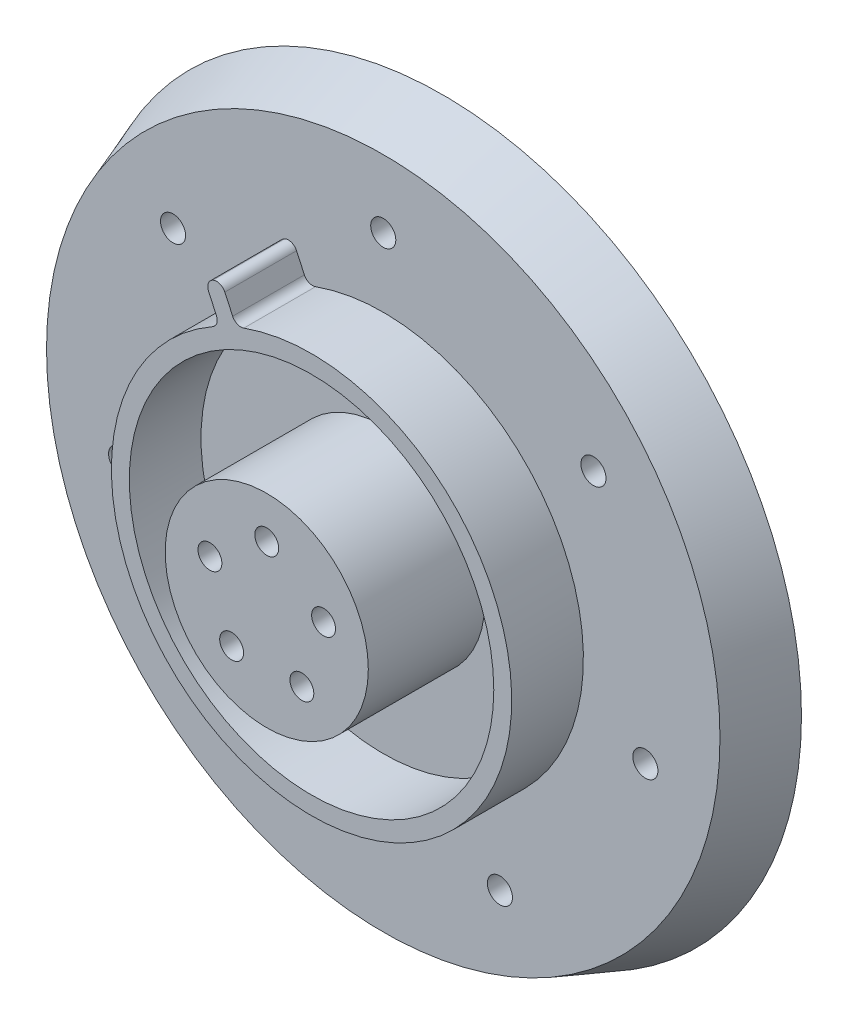
SolidWorks part; units mm, degrees
ref_plane "Plano frontal" through (0, 0, 0) normal (0, 0, 1) x (1, 0, 0)
ref_plane "Plano superior" through (0, 0, 0) normal (0, 1, 0) x (1, 0, 0)
ref_plane "Plano direito" through (0, 0, 0) normal (1, 0, 0) x (0, 0, -1)
sketch "Esboço1" plane through (0, 0, 0) normal (0, 0, 1) x (1, 0, 0)
  circle A0 centre (0, 0) radius 60
  dimension "D1" = 120
extrude "Ressalto-extrusão1" add sketch "Esboço1" along normal blind 10
sketch "Esboço2" plane through (0, 0, 10) normal (0, 0, 1) x (1, 0, 0)
  circle A0 centre (0, 0) radius 17
  dimension "D1" = 34
extrude "Ressalto-extrusão2" add sketch "Esboço2" along normal blind 19.5
sketch "Esboço3" plane through (0, 0, 10) normal (0, 0, 1) x (1, 0, 0)
  line L0 (-13.9923, 30.4379) -> (-16.4984, 35.8895) construction
  line L1 (-17.8613, 35.263) -> (-15.1355, 36.516)
  line L2 (-17.8613, 35.263) -> (-15.3411, 29.7809)
  line L3 (-15.1355, 36.516) -> (-12.6154, 31.0339)
  circle A0 centre (0, 0) radius 30.5
  arc A1 (-15.3411, 29.7809) -> (-12.6154, 31.0339) centre (0, 0) ccw
  point P9 (-16.4984, 35.8895)
  point P12 (-16.4984, 35.8895)
  dimension "D1" = 61
  dimension "D2" = 67
  dimension "D3" = 6
  dimension "D4" = 3
extrude "Ressalto-extrusão3" add sketch "Esboço3" along normal blind 12
sketch "Esboço4" plane through (0, 0, 10) normal (0, 0, 1) x (1, 0, 0)
  circle A0 centre (0, 45) radius 2.1
  circle A6 centre (35.1824, 28.057) radius 2.1
  circle A7 centre (43.8718, -10.0134) radius 2.1
  circle A8 centre (19.5248, -40.5436) radius 2.1
  circle A9 centre (-19.5248, -40.5436) radius 2.1
  circle A10 centre (-43.8718, -10.0134) radius 2.1
  circle A11 centre (-35.1824, 28.057) radius 2.1
  point P16 (0, 0)
  point P18 (0, 0)
  dimension "D1" = 4.2
  dimension "D2" = 45
  dimension "D3" = 7
extrude "Corte-extrusão1" cut sketch "Esboço4" against normal up to surface (10 mm away) up to face at (60, 0, 0)
chamfer "Chanfro1" distance 10 angle 20 1 edges at (60, 0, 10) first distance on face at (60, 0, 10)
sketch "Esboço5" plane through (0, 0, 29.5) normal (0, 0, 1) x (1, 0, 0)
  circle A0 centre (0, 10) radius 2
  circle A1 centre (9.5106, 3.0902) radius 2
  circle A2 centre (5.8779, -8.0902) radius 2
  circle A3 centre (-5.8779, -8.0902) radius 2
  circle A4 centre (-9.5106, 3.0902) radius 2
  point P14 (0, 0)
  dimension "D1" = 4
  dimension "D2" = 10
  dimension "D3" = 5
extrude "Corte-extrusão2" cut sketch "Esboço5" against normal up to surface (29.5 mm away) up to face at (2.1, 45, 0)
chamfer "Chanfro2" distance 3 angle 45 5 edges at (-3.8779, -8.0902, 0) (-7.5106, 3.0902, 0) (2, 10, 0) (11.5106, 3.0902, 0) (7.8779, -8.0902, 0)
fillet "Filete1" radius 1.5 4 edges at (-15.3411, 29.7809, 16) (-17.8613, 35.263, 16) (-15.1355, 36.516, 16) (-12.6154, 31.0339, 16)
